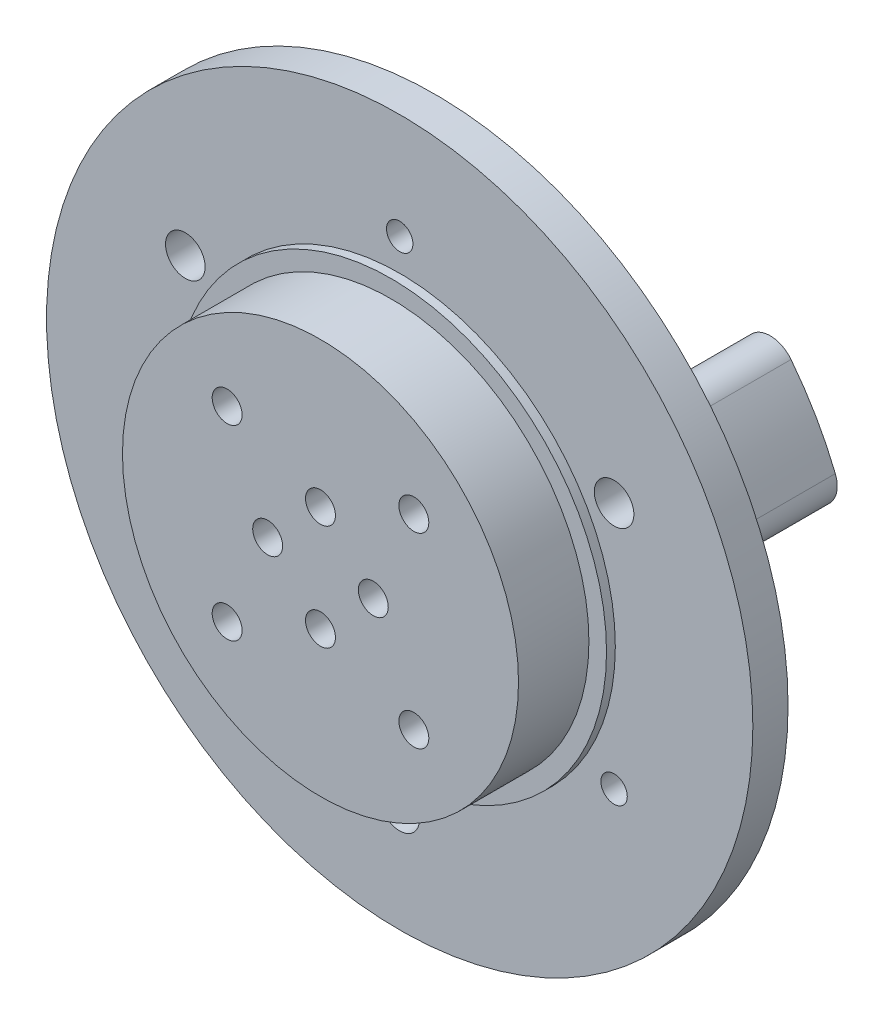
SolidWorks part; units mm, degrees
ref_plane "Front Plane" through (0, 0, 0) normal (0, 0, 1) x (1, 0, 0)
ref_plane "Top Plane" through (0, 0, 0) normal (0, 1, 0) x (1, 0, 0)
ref_plane "Right Plane" through (0, 0, 0) normal (1, 0, 0) x (0, 0, -1)
sketch "Sketch1" plane through (0, 0, 0) normal (0, 0, 1) x (1, 0, 0)
  circle A0 centre (0, 0) radius 28.125 construction
  circle A1 centre (0, 28.125) radius 6
  circle A2 centre (24.357, -14.0625) radius 6
  circle A3 centre (-24.357, -14.0625) radius 6
  circle A4 centre (0, 0) radius 40.125
  point P11 (0, 0)
  dimension "D1" = 56.25
  dimension "D2" = 12
  dimension "D4" = 12
  dimension "D3" = 3
extrude "Boss-Extrude1" add sketch "Sketch1" along normal blind 4 contours A4 A1 A2 A3 | A1 | A3 | A2 region at (0, 28.125, 0) region at (24.357, -14.0625, 0) region at (-24.357, -14.0625, 0) region at (0, 0, 0)
extrude "Boss-Extrude2" add sketch "Sketch1<3>" against normal blind 4.8 contours A1 | A2 | A3 region at (0, 28.125, 0) region at (24.357, -14.0625, 0) region at (-24.357, -14.0625, 0)
sketch "Sketch1<3>" plane through (0, 0, 0) normal (0, 0, 1) x (1, 0, 0) same geometry as "Sketch1"
sketch "Sketch2" plane through (0, 0, 0) normal (0, 0, -1) x (-1, 0, 0)
  circle A0 centre (24.357, -14.0625) radius 6 construction
  circle A1 centre (-24.357, -14.0625) radius 6 construction
  circle A2 centre (0, 28.125) radius 6 construction
  circle A3 centre (24.357, -14.0625) radius 6
  circle A4 centre (-24.357, -14.0625) radius 6
  circle A5 centre (0, 28.125) radius 6
  circle A6 centre (0, 28.125) radius 7
  circle A7 centre (-24.357, -14.0625) radius 7
  circle A8 centre (24.357, -14.0625) radius 7
  dimension "D1" = 1
extrude "Boss-Extrude3" add sketch "Sketch2" along normal blind 1
sketch "Sketch3" plane through (0, 0, 4) normal (0, 0, 1) x (1, 0, 0)
  circle A0 centre (0, 0) radius 22.5
  circle A1 centre (0, 0) radius 24.5
  dimension "D1" = 45
  dimension "D2" = 2
extrude "Boss-Extrude4" add sketch "Sketch3" along normal blind 9 contours A0 region at (0, 0, 4)
extrude "Boss-Extrude5" add sketch "Sketch3<3>" along normal blind 1
sketch "Sketch3<3>" plane through (0, 0, 4) normal (0, 0, 1) x (1, 0, 0) same geometry as "Sketch3"
sketch "Sketch4" plane through (0, 0, 13) normal (0, 0, 1) x (1, 0, 0)
  line L0 (0, 0) -> (-10.6066, 10.6066) construction
  line L1 (0, 0) -> (0, 15) construction
  line L2 (0, 0) -> (-10.6066, 10.6066) construction
  circle A0 centre (0, 0) radius 6 construction
  circle A1 centre (0, 6) radius 1.7
  circle A2 centre (6, 0) radius 1.7
  circle A3 centre (0, -6) radius 1.7
  circle A4 centre (-6, 0) radius 1.7
  circle A5 centre (0, 0) radius 15 construction
  circle A6 centre (-10.6066, 10.6066) radius 1.7
  circle A7 centre (10.6066, 10.6066) radius 1.7
  circle A8 centre (10.6066, -10.6066) radius 1.7
  circle A9 centre (-10.6066, -10.6066) radius 1.7
  point P14 (0, 0)
  dimension "D1" = 12
  dimension "D2" = 3.4
  dimension "D4" = 30
  dimension "D6" = 3.4
  dimension "D5" = 45
  dimension "D8" = 15
  dimension "D3" = 4
  dimension "D7" = 4
extrude "Cut-Extrude1" cut sketch "Sketch4" against normal up to next
sketch "Sketch5" plane through (0, 0, -4.8) normal (0, 0, -1) x (-1, 0, 0)
  line L0 (0, 0) -> (0, 28.125) construction
  circle A0 centre (0, 28.125) radius 1.5
  circle A1 centre (24.357, -14.0625) radius 1.5
  circle A2 centre (-24.357, -14.0625) radius 1.5
  dimension "D1" = 3
  dimension "D3" = 28.125
  dimension "D2" = 3
extrude "Cut-Extrude2" cut sketch "Sketch5" against normal through all
sketch "Sketch7" plane through (0, 0, 0) normal (0, 0, -1) x (-1, 0, 0)
  circle A0 centre (0, 6) radius 2.25
  dimension "D1" = 4.5
extrude "Cut-Extrude4" cut sketch "Sketch7" against normal blind 5
pattern_circular "CirPattern2" count 4 over 360 about axis through (0, 0, 0) along (0, 0, 1) of "Cut-Extrude4"
sketch "Sketch8" plane through (0, 0, 0) normal (0, 0, -1) x (-1, 0, 0)
  line L0 (-17.4288, 10.0625) -> (-34.7493, 20.0625) construction
  line L1 (0, 0) -> (0, 28.125) construction
  line L2 (-34.6996, 10.0477) -> (-18.7559, 7.2961)
  line L3 (-26.0513, 25.0269) -> (-15.6965, 12.595)
  line L4 (0, 0) -> (-25.68, 30.831) construction
  circle A0 centre (0, 28.125) radius 18 construction
  circle A1 centre (24.357, -14.0625) radius 18 construction
  circle A2 centre (-24.357, -14.0625) radius 18 construction
  arc A4 (-34.6996, 10.0477) -> (-26.0513, 25.0269) centre (0, 0) cw
  circle A8 centre (-24.357, 14.0625) radius 1.5
  circle A9 centre (0, 0) radius 40.125 construction
  arc A10 (-18.7559, 7.2961) -> (-15.6965, 12.595) centre (0, 0) cw
  circle A11 centre (0, 0) radius 28.125 construction
  point P9 (0, 0)
  point P20 (0, 0)
  point P23 (0, 0)
  point P24 (-19.2471, 11.1123)
  point P25 (0, 0)
  dimension "D1" = 36
  dimension "D4" = 3
  dimension "D6" = 8
  dimension "D7" = 8
  dimension "D3" = 60
  dimension "D5" = 4
  dimension "D2" = 3
extrude "Boss-Extrude6" add sketch "Sketch8" along normal blind 12
fillet "Fillet1" radius 3 4 edges at (26.0513, 25.0269, -6) (34.6996, 10.0477, -6) (18.7559, 7.2961, -6) (15.6965, 12.595, -6)
extrude "Cut-Extrude5" cut sketch "Sketch8<2>" against normal through all contours A8 region at (24.357, 14.0625, 0)
sketch "Sketch8<2>" plane through (0, 0, 0) normal (0, 0, -1) x (-1, 0, 0) same geometry as "Sketch8"
pattern_circular "CirPattern3" count 3 over 360 about axis through (0, 0, 0) along (0, 0, 1) of "Boss-Extrude6", "Fillet1", "Cut-Extrude5"
sketch "Sketch6" plane through (0, 0, 4) normal (0, 0, 1) x (1, 0, 0)
  circle A0 centre (0, 28.125) radius 2.25
  circle M2 centre (0, 28.125) radius 1.5
  dimension "D1" = 4.5
extrude "Cut-Extrude3" cut sketch "Sketch6" against normal blind 5
pattern_circular "CirPattern1" count 6 over 360 about axis through (0, 0, 4) along (0, 0, 1) skipping 2, 4 of "Cut-Extrude3"
extrude "Boss-Extrude7" add sketch "Sketch6<2>" against normal up to surface (5 mm away) contours A0 M2 region at (-2.1864, 28.125, 4) up to face at (2.25, 28.125, -1)
sketch "Sketch6<2>" plane through (0, 0, 4) normal (0, 0, 1) x (1, 0, 0) same geometry as "Sketch6"
